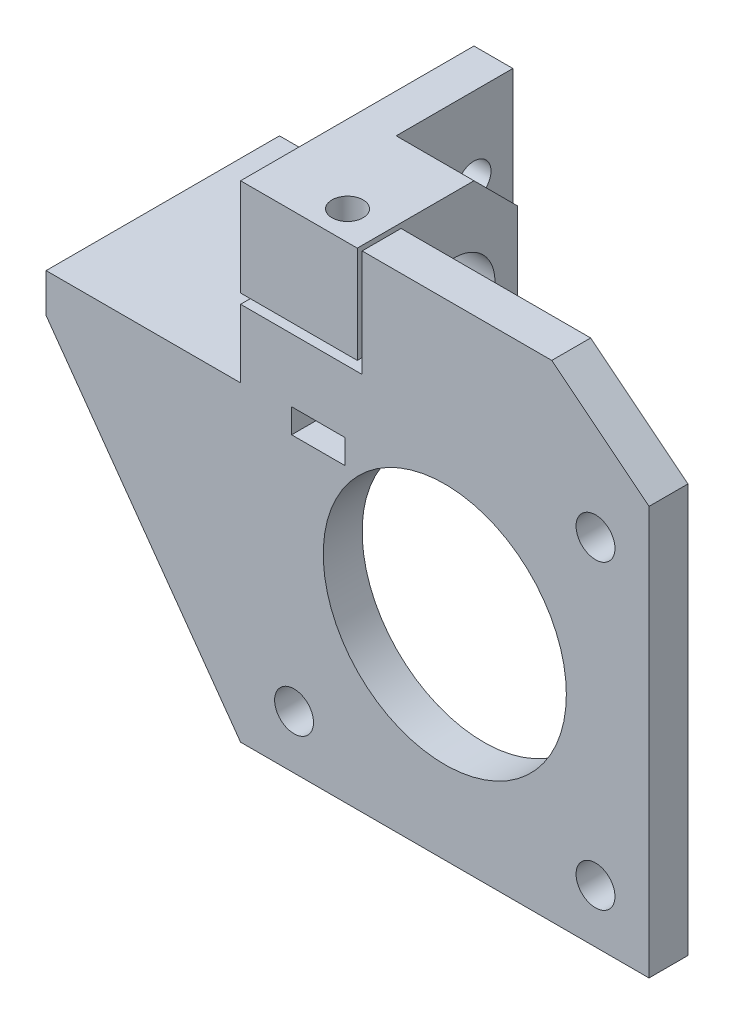
SolidWorks part; units mm, degrees
ref_plane "Plano frontal" through (0, 0, 0) normal (0, 0, 1) x (1, 0, 0)
ref_plane "Plano superior" through (0, 0, 0) normal (0, 1, 0) x (1, 0, 0)
ref_plane "Plano direito" through (0, 0, 0) normal (1, 0, 0) x (0, 0, -1)
sketch "Esboço1" plane through (0, 0, 0) normal (0, 0, 1) x (1, 0, 0)
  line L3 (-49.7252, 0) -> (0, 0) construction
  line L18 (-15.5, 15.5) -> (15.5, -15.5) construction
  line L19 (-15.5, -15.5) -> (15.5, 15.5) construction
  line L20 (15.5, -15.5) -> (15.5, 15.5) construction
  line L21 (-15.5, 15.5) -> (15.5, 15.5) construction
  line L22 (-15.5, -15.5) -> (-15.5, 15.5) construction
  line L23 (-15.5, -15.5) -> (15.5, -15.5) construction
  line L24 (-21, 21) -> (21, -21) construction
  line L25 (-21, -21) -> (21, 21) construction
  line L26 (-41, 7) -> (-21, -21)
  line L27 (11, 29) -> (21, 21)
  line L28 (-21, 29) -> (11, 29)
  line L29 (-21, 21) -> (-21, 29)
  line L30 (-41, 11) -> (-41, 7)
  line L31 (21, -21) -> (21, 21)
  line L32 (-21, 11) -> (-21, 21)
  line L33 (-21, -21) -> (21, -21)
  line L34 (-21, 11) -> (-41, 11)
  circle A3 centre (0, 0) radius 12.5
  circle A4 centre (15.5, 15.5) radius 2
  circle A5 centre (15.5, -15.5) radius 2
  circle A6 centre (-15.5, -15.5) radius 2
  point P0 (0, 0)
  point P1 (0, 0)
  point P2 (0, 0)
  point P3 (0, -15.5)
  point P4 (15.5, 0)
  point P6 (0, 0)
  point P7 (0, 0)
  point P8 (0, 0)
  point P9 (0, 0)
  point P10 (0, 0)
  point P11 (0, 0)
  point P12 (-21.8684, 10.9323)
  point P13 (-37.8137, 101.6603)
  point P16 (0, 0)
  dimension "D2" = 42
  dimension "D5" = 25
  dimension "D3" = 4
  dimension "D1" = 31
  dimension "D4" = 8
  dimension "D6" = 10
  dimension "D7" = 32
  dimension "D8" = 20
  dimension "D9" = 18
  dimension "D10" = 28
extrude "Ressalto-extrusão1" add sketch "Esboço1" along normal blind 4
sketch "Esboço2" plane through (0, 0, 0) normal (0, 0, -1) x (-1, 0, 0)
  line L0 (41, 11) -> (41, 7)
  line L1 (41, 7) -> (21, 7)
  line L2 (17, 11) -> (17, 29)
  line L3 (-11, 29) -> (21, 29) construction
  line L4 (17, 29) -> (21, 29)
  line L5 (21, 29) -> (21, 11)
  line L6 (21, 11) -> (41, 11)
  line L7 (21, 11) -> (41, 11) construction
  line L8 (41, 11) -> (41, 7) construction
  line L9 (41, 7) -> (21, -21) construction
  line L10 (21, 29) -> (21, 11) construction
  arc A0 (17, 11) -> (21, 7) centre (21, 11) ccw
  point P2 (17, 31)
extrude "Ressalto-extrusão2" add sketch "Esboço2" along normal blind 20
sketch "Esboço3" plane through (-17, 0, 0) normal (1, 0, 0) x (0, 0, -1)
  line L0 (0, 29) -> (8, 29)
  line L2 (8, 29) -> (12.5, 24.5)
  line L3 (12.5, 24.5) -> (12.5, 13.5)
  line L4 (12.5, 13.5) -> (8, 9)
  line L5 (20, 29) -> (0, 29) construction
  line L6 (8, 9) -> (0, 9)
  line L7 (0, 9) -> (0, 29)
  line L9 (8, 29) -> (8, 9) construction
  line L10 (0, 29) -> (0, 11) construction
  circle A0 centre (6, 19) radius 4.15
  point P4 (0, 31)
  point P6 (12.5, 19)
  point P10 (13, -31)
  point P11 (0, 0)
  point P13 (13, 13.5443)
  point P14 (12.5, 31)
  point P15 (0, 0)
  point P17 (13, 50.7931)
  point P18 (0, 0)
  point P19 (13, 31)
  dimension "D1" = 8.3
  dimension "D2" = 6
  dimension "D3" = 20
  dimension "D4" = 11
  dimension "D5" = 2
extrude "Ressalto-extrusão3" add sketch "Esboço3" along normal blind 8
sketch "Esboço4" plane through (0, 0, 0) normal (0, 0, -1) x (-1, 0, 0)
  line L0 (9, 19) -> (26.3177, 19)
  line L1 (-11, 29) -> (9, 29) construction
  line L2 (9, 24.5) -> (9, 29) construction
  line L3 (26.3177, 19) -> (26.3177, 15.2911)
  line L4 (26.3177, 15.2911) -> (25.8177, 15.2911)
  line L5 (9, 9) -> (17, 9) construction
  line L6 (25.8177, 15.2911) -> (25.8177, 18)
  line L7 (25.8177, 18) -> (8.5, 18)
  line L8 (8.5, 18) -> (8.5, 29)
  line L9 (8.5, 29) -> (9, 29)
  line L10 (9, 29) -> (9, 19)
  line L11 (9, 9) -> (17, 9) construction
  line L12 (15.75, 11.5) -> (10.25, 11.5)
  line L13 (15.75, 11.5) -> (15.75, 9)
  line L14 (15.75, 9) -> (10.25, 9)
  line L15 (10.25, 11.5) -> (10.25, 9)
  line L16 (15.75, 11.5) -> (10.25, 9) construction
  line L17 (15.75, 9) -> (10.25, 11.5) construction
  point P2 (15.7539, 13)
  point P5 (0, 0)
  point P6 (12.1398, 13)
  point P8 (0, 0)
  point P16 (13, 9)
  point P17 (25.0845, 17)
  point P19 (26.6487, 14.2911)
  point P20 (25.8177, 14.2911)
  point P26 (13, 10.25)
  dimension "D1" = 10
  dimension "D2" = 1
  dimension "D3" = 0.5
  dimension "D4" = 0.5
  dimension "D5" = 2.5
  dimension "D6" = 5.5
extrude "Corte-extrusão1" cut sketch "Esboço4" against normal blind 8 and the other way blind 3
sketch "Esboço5" plane through (-17, 0, 0) normal (1, 0, 0) x (0, 0, -1)
  line L1 (20, 11) -> (20, 29) construction
  line L2 (20, 11) -> (10, 11) construction
  circle A0 centre (16, 21) radius 1.75
  circle A2 centre (6, 19) radius 4.15
  point P2 (21, 20.5271)
  point P10 (11, 22)
  point P11 (0, 0)
  dimension "D3" = 3.5
  dimension "D1" = 10
  dimension "D2" = 4
extrude "Corte-extrusão2" cut sketch "Esboço5" against normal blind 12
sketch "Esboço6" plane through (0, 7, 0) normal (0, -1, 0) x (-1, 0, 0)
  line L1 (21, 20) -> (41, 20) construction
  line L2 (21, 20) -> (21, 0) construction
  circle A0 centre (31.5, 13) radius 1.75
  circle A1 centre (31.5, -7) radius 1.75
  point P4 (29.9789, 18)
  dimension "D2" = 3.5
  dimension "D1" = 20
  dimension "D3" = 10.5
  dimension "D4" = 7
extrude "Corte-extrusão3" cut sketch "Esboço6" against normal blind 12
sketch "Esboço7" plane through (0, 9, 0) normal (0, -1, 0) x (1, 0, 0)
  line L0 (-9, -8) -> (-17, -8) construction
  line L2 (-9, 0) -> (-10.25, 0) construction
  circle A0 centre (-13, 1) radius 1.6
  point P2 (0, 0)
  point P5 (-13, -8)
  dimension "D2" = 3.2
  dimension "D1" = 1
extrude "Corte-extrusão4" cut sketch "Esboço7" against normal through all
